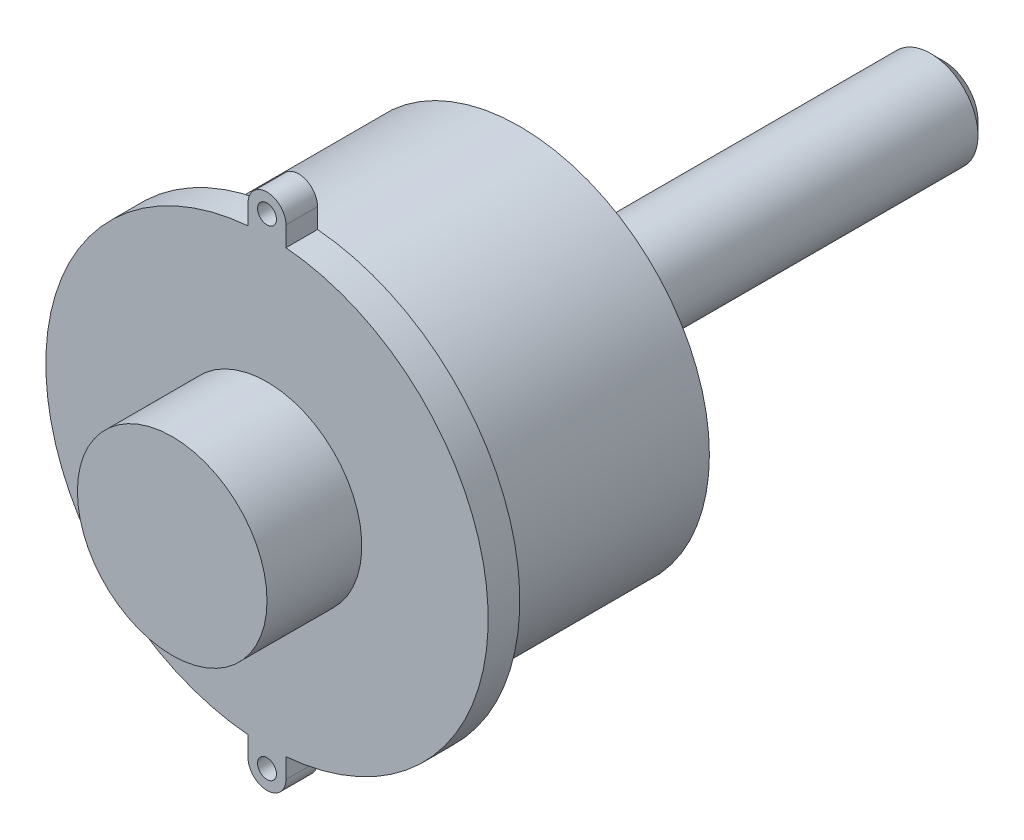
SolidWorks part; units mm, degrees
ref_plane "Ön Düzlem" through (0, 0, 0) normal (0, 0, 1) x (1, 0, 0)
ref_plane "Üst Düzlem" through (0, 0, 0) normal (0, 1, 0) x (1, 0, 0)
ref_plane "Sağ Düzlem" through (0, 0, 0) normal (1, 0, 0) x (0, 0, -1)
sketch "Sketch1" plane through (0, 0, 0) normal (0, 0, 1) x (1, 0, 0)
  line L0 (0, 38) -> (0, -38) construction
  line L1 (-38, 0) -> (38, 0) construction
  line L2 (-3, 38) -> (-3, 34.8712)
  line L3 (3, 38) -> (3, 34.8712)
  line L4 (3, -38) -> (3, -34.8712)
  line L5 (-3, -38) -> (-3, -34.8712)
  arc A0 (-3, 34.8712) -> (-3, -34.8712) centre (0, 0) ccw
  circle A1 centre (0, 0) radius 38 construction
  circle A2 centre (0, 38) radius 1.5
  arc A3 (-3, 38) -> (3, 38) centre (0, 38) cw
  circle A4 centre (0, -38) radius 1.5
  arc A5 (-3, -38) -> (3, -38) centre (0, -38) ccw
  arc A6 (3, -34.8712) -> (3, 34.8712) centre (0, 0) ccw
  dimension "D1" = 35
  dimension "D2" = 76
  dimension "D3" = 3
  dimension "D4" = 3
extrude "Boss-Extrude1" add sketch "Sketch1" against normal blind 5
sketch "Sketch2" plane through (0, 0, 0) normal (0, 0, 1) x (1, 0, 0)
  circle A0 centre (0, 0) radius 15
  dimension "D1" = 30
extrude "Boss-Extrude2" add sketch "Sketch2" along normal blind 15
sketch "Sketch3" plane through (0, 0, -5) normal (0, 0, -1) x (-1, 0, 0)
  circle A0 centre (0, 0) radius 30
  dimension "D1" = 60
extrude "Boss-Extrude3" add sketch "Sketch3" along normal blind 35
sketch "Sketch4" plane through (0, 0, -40) normal (0, 0, -1) x (-1, 0, 0)
  circle A0 centre (0, 0) radius 10
  dimension "D1" = 20
ref_plane "Plane1" through (0, 0, -47) normal (0, 0, -1) x (-1, 0, 0)
sketch "Sketch5" plane through (0, 0, -47) normal (0, 0, -1) x (-1, 0, 0)
  circle A0 centre (0, 0) radius 7.5
  dimension "D1" = 15
loft "Loft1" add profiles "Sketch4", "Sketch5" connector at (4.1323, 9.1063, -40) connector at (5.3299, 5.2766, -47)
sketch "Sketch6" plane through (0, 0, -47) normal (0, 0, -1) x (-1, 0, 0)
  circle A1 centre (0, 0) radius 7.5
  circle A2 centre (0, 0) radius 7.5
  dimension "D1" = 0
extrude "Boss-Extrude5" add sketch "Sketch6" along normal blind 60
chamfer "Chamfer2" distance 2 angle 45 1 edges at (-7.5, 0, -107)
